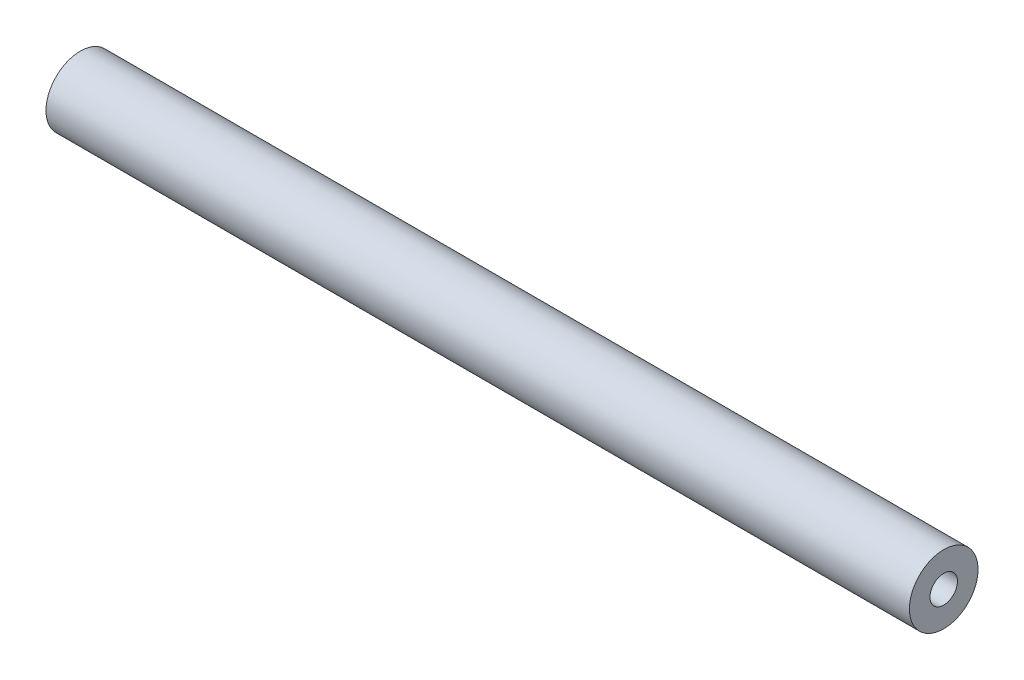
SolidWorks part; units mm, degrees
ref_plane "Front" through (0, 0, 0) normal (0, 0, 1) x (1, 0, 0)
ref_plane "Top" through (0, 0, 0) normal (0, 1, 0) x (1, 0, 0)
ref_plane "Right" through (0, 0, 0) normal (1, 0, 0) x (0, 0, -1)
sketch "Sketch1" plane through (0, 0, 0) normal (1, 0, 0) x (0, 0, -1)
  circle A0 centre (0, 0) radius 12.7
  circle A1 centre (0, 0) radius 31.75
  dimension "D1" = 25.4
  dimension "D2" = 63.5
extrude "Boss-Extrude1" add sketch "Sketch1" along normal mid plane 798.5125
